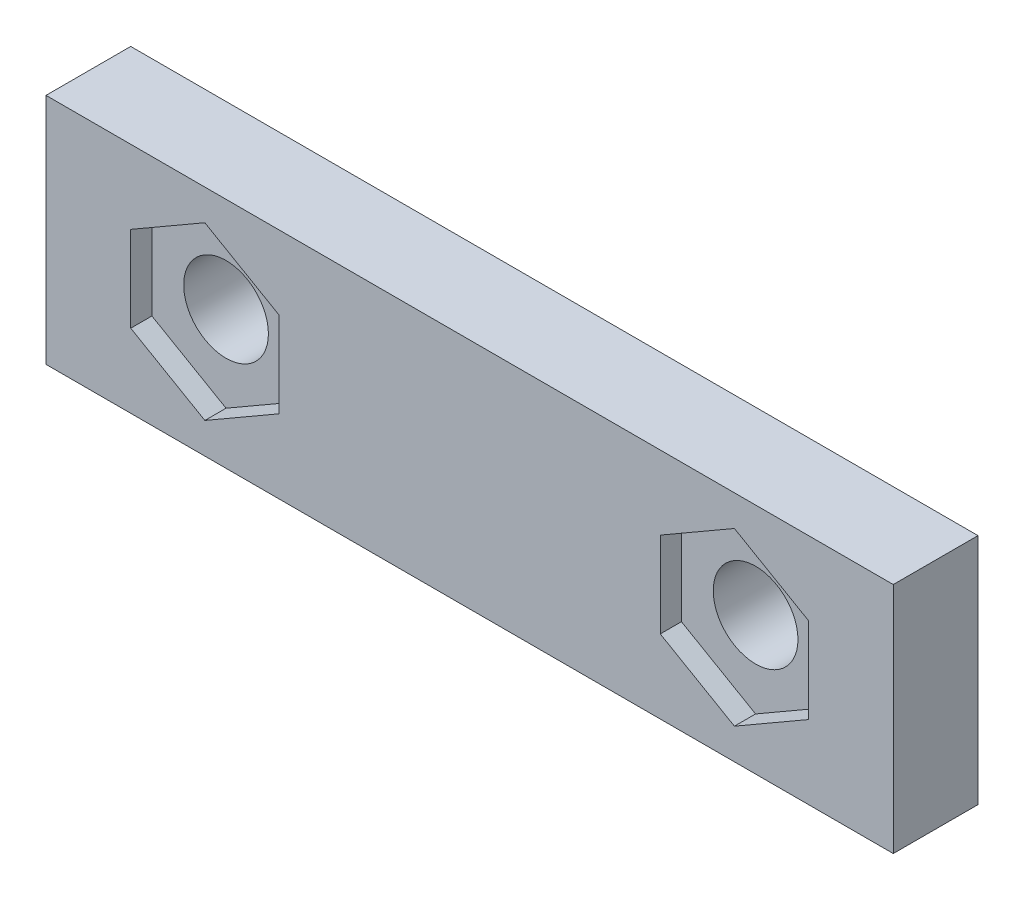
SolidWorks part; units mm, degrees
ref_plane "Front Plane" through (0, 0, 0) normal (0, 0, 1) x (1, 0, 0)
ref_plane "Top Plane" through (0, 0, 0) normal (0, 1, 0) x (1, 0, 0)
ref_plane "Right Plane" through (0, 0, 0) normal (1, 0, 0) x (0, 0, -1)
sketch "Sketch1" plane through (0, 0, 0) normal (0, 0, 1) x (1, 0, 0)
  line L0 (174.6, -50.5) -> (225, -50.5) construction
  line L1 (219.8, -39.5) -> (179.8, -39.5)
  line L2 (219.8, -39.5) -> (219.8, -50.5)
  line L3 (219.8, -50.5) -> (179.8, -50.5)
  line L4 (179.8, -39.5) -> (179.8, -50.5)
  line L5 (219.8, -39.5) -> (179.8, -50.5) construction
  line L6 (219.8, -50.5) -> (179.8, -39.5) construction
  line L8 (212.3, -49.0415) -> (215.8, -47.0207)
  line L9 (215.8, -47.0207) -> (215.8, -42.9793)
  line L10 (215.8, -42.9793) -> (212.3, -40.9585)
  line L11 (212.3, -40.9585) -> (208.8, -42.9793)
  line L12 (208.8, -42.9793) -> (208.8, -47.0207)
  line L13 (208.8, -47.0207) -> (212.3, -49.0415)
  line L14 (187.3, -49.0415) -> (190.8, -47.0207)
  line L15 (190.8, -47.0207) -> (190.8, -42.9793)
  line L16 (190.8, -42.9793) -> (187.3, -40.9585)
  line L17 (187.3, -40.9585) -> (183.8, -42.9793)
  line L18 (183.8, -42.9793) -> (183.8, -47.0207)
  line L19 (183.8, -47.0207) -> (187.3, -49.0415)
  circle A0 centre (212.3, -45) radius 2
  circle A1 centre (187.3, -45) radius 2
  circle A2 centre (212.3, -45) radius 3.5 construction
  circle A3 centre (187.3, -45) radius 3.5 construction
  point P4 (199.8, -45)
  point P13 (185.55, -41.9689)
  dimension "D4" = 4
  dimension "D5" = 4
  dimension "D1" = 5.5
  dimension "D2" = 40
  dimension "D3" = 7.5
  dimension "D6" = 7
  dimension "D7" = 7
extrude "Boss-Extrude1" add sketch "Sketch1" along normal blind 3 contours L1 L4 L3 L2 L19 L18 L17 L16 L15 L14 L13 L12 L11 L10 L9 L8 | L18 L19 L14 L15 L16 L17 A1 | L12 L13 L8 L9 L10 L11 A0 region at (199.8, -45, 0) region at (210.6035, -47.9385, 0) region at (185.6035, -47.9385, 0)
extrude "Boss-Extrude2" add sketch "Sketch1<3>" along normal blind 4 contours L1 L4 L3 L2 L19 L18 L17 L16 L15 L14 L13 L12 L11 L10 L9 L8 region at (199.8, -45, 0)
sketch "Sketch1<3>" plane through (0, 0, 0) normal (0, 0, 1) x (1, 0, 0) same geometry as "Sketch1"
